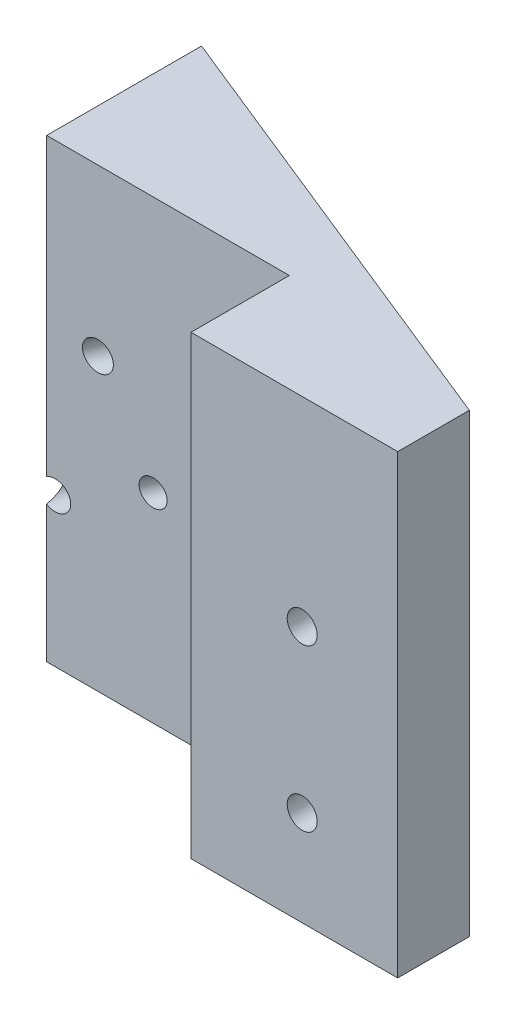
SolidWorks part; units mm, degrees
ref_plane "Front" through (0, 0, 0) normal (0, 0, 1) x (1, 0, 0)
ref_plane "Top" through (0, 0, 0) normal (0, 1, 0) x (1, 0, 0)
ref_plane "Right" through (0, 0, 0) normal (1, 0, 0) x (0, 0, -1)
sketch "Sketch1" plane through (0, 0, 0) normal (0, 1, 0) x (1, 0, 0)
  line L0 (69, 5) -> (0, 32.8778)
  line L3 (0, 5) -> (69, 5)
  line L5 (0, 32.8778) -> (0, 5)
  line L7 (0, 5) -> (69, 5)
  line L8 (0, 5) -> (0, 0)
  line L9 (0, 0) -> (69, 0)
  line L10 (69, 5) -> (69, 0)
  dimension "D1" = 5
  dimension "D2" = 22
  dimension "D3" = 69
extrude "Boss-Extrude1" add sketch "Sketch1" along normal blind 70 contours L0 L5 L3 | L9 L3 region at (23, 0, -14.2926) region at (34.5, 0, -2.5)
sketch "Sketch2" plane through (0, 70, 0) normal (0, 1, 0) x (1, 0, 0)
  line L0 (0, 32.8778) -> (0, 0) construction
  line L1 (0, 9.1) -> (37.2614, 9.1)
  line L2 (0, 9.1) -> (0, 0)
  line L3 (0, 0) -> (37.2614, 0)
  line L4 (37.2614, 9.1) -> (37.2614, 0)
  line L5 (37.2614, 9.1) -> (-18.9926, 9.1) construction
  line L6 (0, 0) -> (69, 0) construction
  line L7 (37.2614, -6) -> (37.2614, 4) construction
sketch "Sketch3" plane through (0, 70, 0) normal (0, 1, 0) x (1, 0, 0)
  line L0 (0, 32.8778) -> (0, 0) construction
  line L1 (0, 9.1) -> (37.2614, 9.1)
  line L2 (0, 9.1) -> (0, 0)
  line L3 (0, 0) -> (37.2614, 0)
  line L4 (37.2614, 9.1) -> (37.2614, 0)
  dimension "D1" = 9.1
extrude "Cut-Extrude1" cut sketch "Sketch3" against normal blind 70
sketch "Sketch4" plane through (0, 70, 0) normal (0, 1, 0) x (1, 0, 0)
  line L1 (37.2614, 0) -> (69, 0)
  line L2 (37.2614, 0) -> (37.2614, -6)
  line L3 (37.2614, -6) -> (69, -6)
  line L4 (69, 0) -> (69, -6)
  dimension "D1" = 6
extrude "Boss-Extrude2" add sketch "Sketch4" against normal blind 70
sketch "Sketch5" plane through (0, 0, 6) normal (0, 0, 1) x (1, 0, 0)
  circle A0 centre (54.3369, 39.3863) radius 2.3
  circle A1 centre (54.3369, 14.6087) radius 2.3
extrude "Cut-Extrude2" cut sketch "Sketch5" against normal blind 20
sketch "Sketch6" plane through (11.4194, 0, -28.2641) normal (0.3746, 0, -0.9272) x (-0.9272, 0, -0.3746)
  circle A0 centre (10.051, 36.7333) radius 2.2
  circle A1 centre (2.1915, 22.7967) radius 2.2
  circle A2 centre (-3.8855, 44.5928) radius 2.2
  circle A3 centre (-11.745, 30.6563) radius 2
extrude "Cut-Extrude3" cut sketch "Sketch6" against normal blind 45
